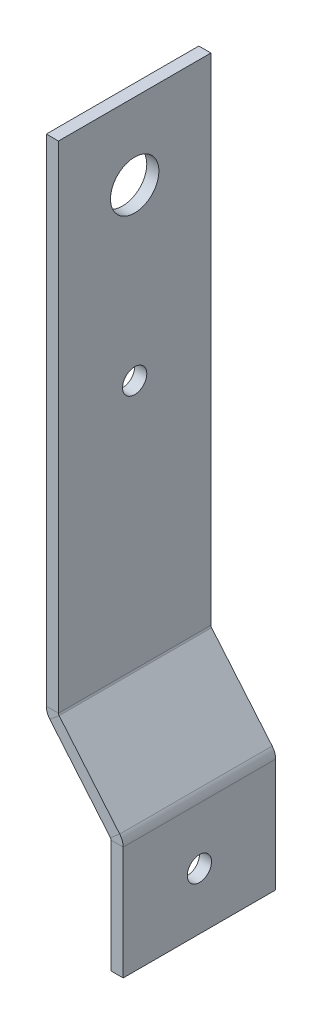
SolidWorks part; units mm, degrees
note: The reader was unsure of these and kept them because the rebuilt part matched: thickness of "Base-Flange1", "Edge-Flange1", "Edge-Flange2", "Sheet-Metal1", "Sheet-Metal2", "Sheet-Metal3", "Sheet-Metal6"; flange length of "Edge-Flange1", "Edge-Flange2".
ref_plane "Front Plane" through (0, 0, 0) normal (0, 0, 1) x (1, 0, 0)
ref_plane "Top Plane" through (0, 0, 0) normal (0, 1, 0) x (1, 0, 0)
ref_plane "Right Plane" through (0, 0, 0) normal (1, 0, 0) x (0, 0, -1)
sketch "Sketch1" plane through (0, 0, 0) normal (1, 0, 0) x (0, 0, -1)
  line L0 (0, 0) -> (40, 0)
  line L1 (40, 0) -> (40, -130)
  line L2 (40, -130) -> (0, -130)
  line L3 (0, -130) -> (0, 0)
  line L4 (20, 0) -> (20, -130) construction
  circle A0 centre (20, -20) radius 6.35
  circle A1 centre (20, -64.45) radius 3.175
  dimension "D3" = 12.7
  dimension "D4" = 6.35
  dimension "D1" = 40
  dimension "D2" = 130
  dimension "D5" = 20
  dimension "D6" = 44.45
base flange "Base-Flange1" sketch "Sketch1" thickness 3.175 reverse thickness direction no parameters "D1"=0.7366
edge flange "Edge-Flange1" sketch "Sketch10" flange angle 140 flange length 25 flange position bend outside bend radius 0.7366 thickness 3.175 relief rectangular parameters "D6"=10
sketch "Sketch10" plane through (0, -130, 0) normal (-0.766, -0.6428, 0) x (0, 0, -1)
  line L2 (0, 0) -> (0, 25)
  line L3 (0, 25) -> (40, 25)
  line L4 (40, 25) -> (40, 0)
  line L15 (0, 0) -> (40, 0) construction
  line L16 (0, 0) -> (40, 0)
bend "EdgeBend1" bend radius 0.7366 bend angle 40 parameters "D5"=1
edge flange "Edge-Flange2" sketch "Sketch13" flange angle 140 flange length 30 flange position bend outside bend radius 0.7366 thickness 3.175 relief rectangular parameters "D6"=10
sketch "Sketch13" plane through (13.6375, -151.4601, 0) normal (1, 0, 0) x (0, 0, 1)
  line L0 (-40, 0) -> (0, 0) construction
  line L1 (-40, 0) -> (0, 0)
  line L2 (-40, 0) -> (-40, 30)
  line L3 (-40, 30) -> (0, 30)
  line L4 (0, 30) -> (0, 0)
bend "EdgeBend2" bend radius 0.7366 bend angle 40 parameters "D5"=2
sketch "Sketch20" plane through (16.9848, 0, 0) normal (1, 0, 0) x (0, 0, -1)
  line L0 (20, -151.9335) -> (20, -181.6654) construction
  line L6 (0, -151.9335) -> (40, -151.9335) construction
  line L7 (0, -181.6654) -> (40, -181.6654) construction
  circle A1 centre (20, -166.7995) radius 3.175
  point P6 (20, -166.7995)
  dimension "D1" = 6.35
extrude "Cut-Extrude3" cut sketch "Sketch20" against normal up to surface (3.175 mm away) normal cut yes up to face at (13.8098, -166.7995, -20)
sketch "Bend-Lines1" [suppressed] plane through (0, 0, 0) normal (0, 1, 0) x (1, 0, 0)
sketch "Bounding-Box1" [suppressed] plane through (0, 0, 0) normal (0, 1, 0) x (1, 0, 0)
sheet metal parameters "Sheet-Metal1" thickness 3.175 parameters "D1"=0.7366
flat pattern "Flat-Pattern1" [suppressed]
sketch "Bend-Lines2" plane through (0, 0, 0) normal (0, 1, 0) x (1, 0, 0)
sketch3d "Bounding-Box2" [suppressed]
  line L0 (0, 0, 0) -> (0, -100, 0) construction
  line L1 (40, 0, 0) -> (40, -100, 0) construction
  line L2 (0, 0, 0) -> (40, 0, 0) construction
  line L3 (0, -100, 0) -> (40, -100, 0) construction
sheet metal parameters "Sheet-Metal2" thickness 3.175 parameters "D1"=0.7366, "D7"=6.35
flat pattern "Flat-Pattern1" [suppressed]
sketch "Bend-Lines2" plane through (0, 0, 0) normal (1, 0, 0) x (0, 0, -1)
  line L0 (0, -131.0241) -> (40, -131.0241) construction
  line L1 (0, -131.0241) -> (40, -131.0241) construction
sketch3d "Bounding-Box2" [suppressed]
  line L0 (0, 0, 0) -> (0, -170.1493, 0) construction
  line L1 (40, 0, 0) -> (40, -170.1493, 0) construction
  line L2 (0, 0, 0) -> (40, 0, 0) construction
  line L3 (0, -170.1493, 0) -> (40, -170.1493, 0) construction
bend of the flat pattern "EdgeBend1>1"
sketch "Sketch16-2" plane through (0, -19.0965, 0) normal (1, 0, 0) x (0, 0, -1)
  line L0 (0, -132.0022) -> (40, -132.0022) construction
  circle A0 centre (20, -132.0022) radius 3.175
  dimension "D1" = 6.35
sheet metal parameters "Sheet-Metal3" thickness 3.175 parameters "D1"=0.7366, "D7"=6.35
flat pattern "Flat-Pattern1" [suppressed]
sketch "Bend-Lines2" plane through (0, 0, 0) normal (1, 0, 0) x (0, 0, -1)
  line L0 (0, -131.3654) -> (40, -131.3654) construction
  line L1 (0, -131.3654) -> (40, -131.3654) construction
  line L2 (0, -151.5169) -> (40, -151.5169) construction
  line L3 (0, -151.5169) -> (40, -151.5169) construction
sketch3d "Bounding-Box2" [suppressed]
  line L0 (0, 0, 0) -> (0, -175.622, 0) construction
  line L1 (40, 0, 0) -> (40, -175.622, 0) construction
  line L2 (0, 0, 0) -> (40, 0, 0) construction
  line L3 (0, -175.622, 0) -> (40, -175.622, 0) construction
bend of the flat pattern "EdgeBend1>1"
bend of the flat pattern "EdgeBend2>1"
sheet metal parameters "Sheet-Metal6" thickness 3.175 parameters "D1"=0.7366, "D7"=6.35
flat pattern "Flat-Pattern1"
sketch "Bend-Lines2" plane through (0, 0, 0) normal (1, 0, 0) x (0, 0, -1)
  line L0 (0, -130.8113) -> (40, -130.8113) construction
  line L1 (0, -130.8113) -> (40, -130.8113) construction
  line L2 (0, -157.1657) -> (40, -157.1657) construction
  line L3 (0, -157.1657) -> (40, -157.1657) construction
sketch3d "Bounding-Box2" [suppressed]
  line L0 (0, 0, 0) -> (0, -187.7089, 0) construction
  line L1 (40, 0, 0) -> (40, -187.7089, 0) construction
  line L2 (0, 0, 0) -> (40, 0, 0) construction
  line L3 (0, -187.7089, 0) -> (40, -187.7089, 0) construction
bend of the flat pattern "EdgeBend1>1"
bend of the flat pattern "EdgeBend2>1"
